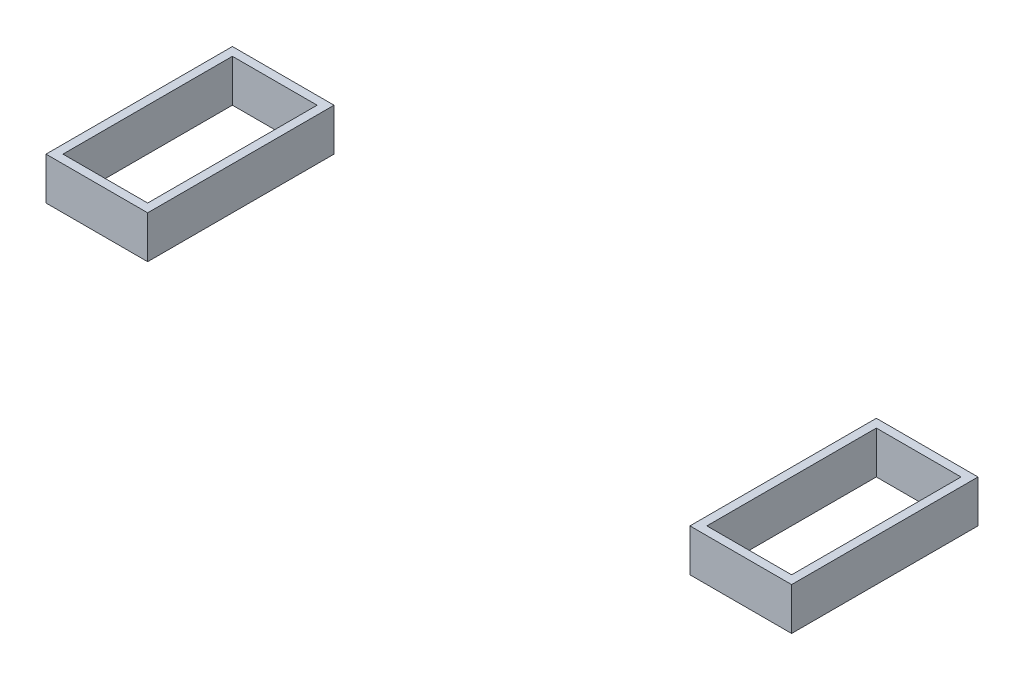
SolidWorks part; units mm, degrees
ref_plane "Front Plane" through (0, 0, 0) normal (0, 0, 1) x (1, 0, 0)
ref_plane "Top Plane" through (0, 0, 0) normal (0, 1, 0) x (1, 0, 0)
ref_plane "Right Plane" through (0, 0, 0) normal (1, 0, 0) x (0, 0, -1)
ref_plane "Plane1" through (0, 60, 0) normal (0, 1, 0) x (1, 0, 0)
sketch "Sketch2" plane through (0, 60, 0) normal (0, 1, 0) x (1, 0, 0)
  line L16 (-38, -40) -> (-38, -60) construction
  line L17 (-43, -40) -> (-33, -40)
  line L18 (-43, -40) -> (-43, -60)
  line L19 (-43, -60) -> (-33, -60)
  line L20 (-33, -40) -> (-33, -60)
  line L21 (33, -40) -> (43, -40)
  line L22 (33, -40) -> (33, -60)
  line L23 (33, -60) -> (43, -60)
  line L24 (43, -40) -> (43, -60)
  line L25 (-43, -50) -> (-33, -50) construction
  line L26 (38, -40) -> (38, -60) construction
  line L27 (0, 49.1392) -> (0, -49.1392) construction
  line L29 (43, -50) -> (33, -50) construction
  line L30 (-32, -39) -> (-32, -61)
  line L31 (-44, -61) -> (-32, -61)
  line L32 (-44, -39) -> (-44, -61)
  line L33 (-44, -39) -> (-32, -39)
  line L34 (32, -39) -> (32, -61)
  line L35 (32, -61) -> (44, -61)
  line L36 (44, -39) -> (44, -61)
  line L37 (32, -39) -> (44, -39)
  dimension "D1" = 10
  dimension "D2" = 20
  dimension "D3" = 10
  dimension "D4" = 20
  dimension "D5" = 33
  dimension "D6" = 33
  dimension "D7" = 60
  dimension "D8" = 1
  dimension "D9" = 1
extrude "Boss-Extrude1" add sketch "Sketch2" along normal blind 5
sketch "Sketch9" plane through (0, 60, 0) normal (0, -1, 0) x (1, 0, 0)
  line L1 (-33, 60) -> (-43, 60)
  line L2 (-33, 60) -> (-33, 40)
  line L3 (-33, 40) -> (-43, 40)
  line L4 (-43, 60) -> (-43, 40)
  line L5 (-33, 60) -> (-43, 40) construction
  line L6 (-33, 40) -> (-43, 60) construction
  point P6 (-44, -11)
  point P8 (-43, -10)
  point P10 (0, 0)
  point P11 (-32.5347, 40.4888)
  point P12 (-43, 40)
  point P14 (-33, 60)
  point P16 (0, 0)
ref_plane "Plane2" through (-12, 0, 0) normal (1, 0, 0) x (0, 0, -1)
sketch "Sketch11" plane through (-12, 0, 0) normal (1, 0, 0) x (0, 0, -1)
  line L1 (10, -5) -> (-10, -5)
  line L2 (10, -5) -> (10, 5)
  line L3 (10, 5) -> (-10, 5)
  line L4 (-10, -5) -> (-10, 5)
  line L5 (10, -5) -> (-10, 5) construction
  line L6 (10, 5) -> (-10, -5) construction
  point P0 (0, 0)
  dimension "D1" = 20
  dimension "D2" = 10
sketch3d "3DSketch1"
  line L0 (-38, 60, 50) -> (-38, 40, 50)
  line L1 (-38, 60, 40) -> (-38, 60, 60) construction
  line L2 (-12, 0, 0) -> (-24.8465, 0, 0)
  line L4 (-24.8465, 0, 0) -> (-38, 40, 50)
  line L5 (-12, -5, -10) -> (-12, 5, 10) construction
  dimension "D2" = 20
